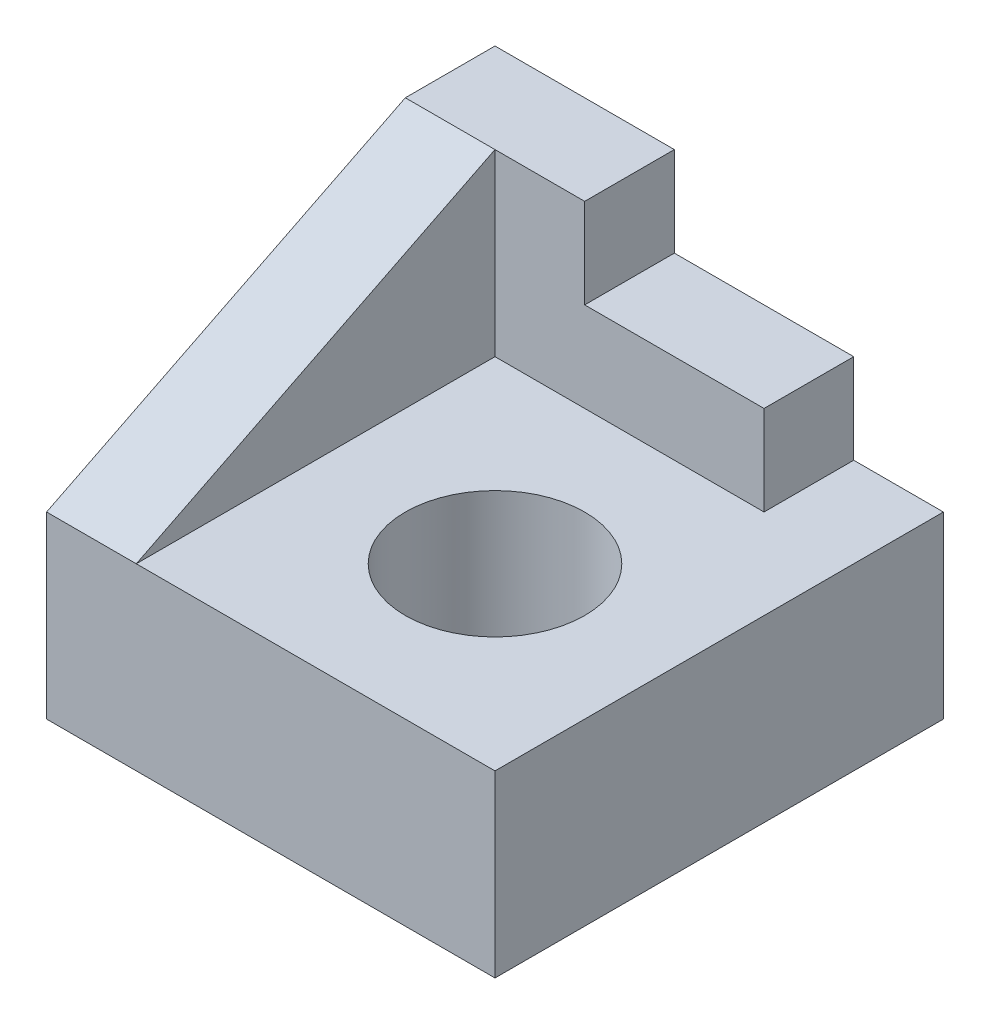
SolidWorks part; units mm, degrees
ref_plane "前基準面" through (0, 0, 0) normal (0, 0, 1) x (1, 0, 0)
ref_plane "上基準面" through (0, 0, 0) normal (0, 1, 0) x (1, 0, 0)
ref_plane "右基準面" through (0, 0, 0) normal (1, 0, 0) x (0, 0, -1)
sketch "草圖1" plane through (0, 0, 0) normal (0, 1, 0) x (1, 0, 0)
  line L1 (-15, 15) -> (10, 15)
  line L2 (-15, 15) -> (-15, -10)
  line L3 (-15, -10) -> (10, -10)
  line L4 (10, 15) -> (10, -10)
  line L5 (-15, 15) -> (-5, 15)
  line L6 (-15, 15) -> (-15, 10)
  line L7 (-15, 10) -> (-5, 10)
  line L8 (-5, 15) -> (-5, 10)
  line L9 (-5, 10) -> (5, 10)
  line L10 (-5, 10) -> (-5, 15)
  line L11 (-5, 15) -> (5, 15)
  line L12 (5, 10) -> (5, 15)
  line L13 (-15, 10) -> (-10, 10)
  line L14 (-15, 10) -> (-15, -10)
  line L15 (-15, -10) -> (-10, -10)
  line L16 (-10, 10) -> (-10, -10)
  circle A0 centre (0, 0) radius 5
  dimension "D9" = 10
  dimension "D1" = 10
  dimension "D2" = 10
  dimension "D3" = 25
  dimension "D4" = 25
  dimension "D5" = 5
  dimension "D6" = 10
  dimension "D7" = 10
  dimension "D8" = 5
extrude "填料-伸長1" add sketch "草圖1" along normal blind 10 contours L7 L16 L3 L4 L1 L12 L9 A0 region at (7.5, 0, -14.6798)
extrude "填料-伸長2" add sketch "草圖1<3>" along normal blind 15 contours L9 L12 L1 L8 region at (0, 0, -12.5)
sketch "草圖1<3>" plane through (0, 0, 0) normal (0, 1, 0) x (1, 0, 0) same geometry as "草圖1"
extrude "填料-伸長3" add sketch "草圖1<4>" along normal blind 20 contours L8 L1 L2 L7 | L16 L7 L2 L3 region at (-10, 0, -12.5) region at (-12.5, 0, 0)
sketch "草圖1<4>" plane through (0, 0, 0) normal (0, 1, 0) x (1, 0, 0) same geometry as "草圖1"
sketch "草圖2" plane through (-10, 0, 0) normal (1, 0, 0) x (0, 0, -1)
  line L0 (-10, 10) -> (10, 20)
  line L1 (-10, 20) -> (-10, 10) construction
  line L2 (10, 20) -> (-10, 20) construction
  line L3 (10, 20) -> (-10, 20)
  line L4 (-10, 20) -> (-10, 10)
  dimension "D1" = 10
extrude "除料-伸長1" cut sketch "草圖2" against normal blind 20
scale "縮放比例1" scale about centroid uniform scaling yes scale factor 0.2
